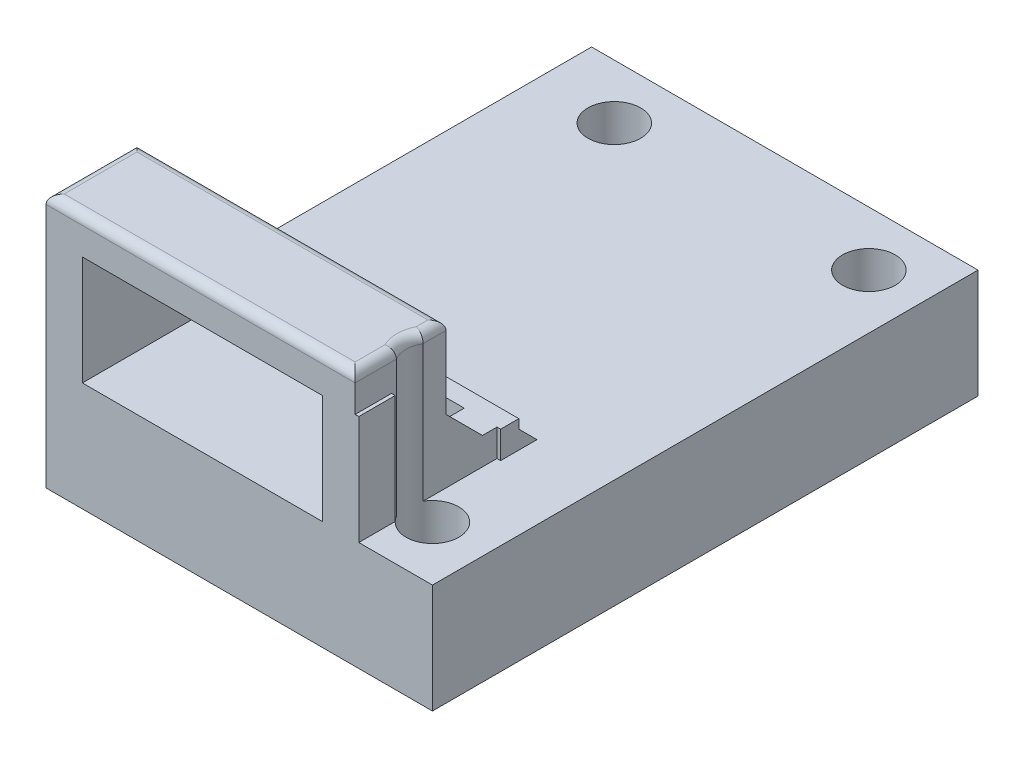
SolidWorks part; units mm, degrees
ref_plane "前视基准面" through (0, 0, 0) normal (0, 0, 1) x (1, 0, 0)
ref_plane "上视基准面" through (0, 0, 0) normal (0, 1, 0) x (1, 0, 0)
ref_plane "右视基准面" through (0, 0, 0) normal (1, 0, 0) x (0, 0, -1)
other "Configuration Table"
sketch "草图1" plane through (0, 0, 0) normal (0, 1, 0) x (1, 0, 0)
  line L0 (-21.25, 0) -> (-21.25, -5)
  line L2 (0, 0) -> (0, 10)
  line L3 (0, 10) -> (-21.25, 10)
  line L5 (-21.25, -5) -> (-6.25, -5)
  line L6 (-6.25, -5) -> (-6.25, 0)
  line L8 (-6.25, 0) -> (0, 0)
  line L10 (-21.25, 0) -> (-21.25, 10)
  dimension "D1" = 21.25
  dimension "D4" = 6.25
  dimension "D5" = 5
  dimension "D6" = 5
extrude "凸台-拉伸1" add sketch "草图1" along normal blind 4
sketch "草图7" plane through (0, 0, -10) normal (0, 0, -1) x (-1, 0, 0)
  line L1 (0, 4) -> (21.25, 4)
  line L2 (0, 4) -> (0, 0)
  line L3 (0, 0) -> (21.25, 0)
  line L4 (21.25, 4) -> (21.25, 0)
extrude "凸台-拉伸3" add sketch "草图7" along normal blind 15
sketch "草图8" plane through (0, 4, 0) normal (0, 1, 0) x (1, 0, 0)
  line L0 (0, 25) -> (-3, 25) construction
  line L1 (-21.25, 25) -> (0, 25) construction
  line L2 (-3, 25) -> (-17, 25) construction
  line L3 (-17, 25) -> (-17, 22) construction
  line L4 (-3, 25) -> (-3, 22) construction
  circle A2 centre (-17, 22) radius 1.45
  circle A3 centre (-3, 22) radius 1.45
  dimension "D3" = 3
  dimension "D5" = 2.9
  dimension "D6" = 2.9
  dimension "D1" = 3
  dimension "D2" = 14
  dimension "D4" = 3
extrude "切除-拉伸5" cut sketch "草图8" against normal blind 5
sketch "草图9" plane through (0, 0, 0) normal (0, 0, 1) x (1, 0, 0)
  line L1 (-6.25, 4) -> (0, 4)
  line L2 (-6.25, 4) -> (-6.25, 0)
  line L3 (-6.25, 0) -> (0, 0)
  line L4 (0, 4) -> (0, 0)
extrude "凸台-拉伸4" add sketch "草图9" along normal up to surface (5 mm away) up to face at (-13.75, 2, 5)
sketch "草图10" plane through (0, 4, 0) normal (0, 1, 0) x (1, 0, 0)
  line L0 (0, -5) -> (-3, -5) construction
  line L2 (-3, -5) -> (-3, -2) construction
  circle A0 centre (-3, -2) radius 1.45
  dimension "D3" = 2.9
  dimension "D1" = 3
  dimension "D2" = 3
extrude "切除-拉伸6" cut sketch "草图10" against normal blind 5
sketch "草图11" plane through (0, 4, 0) normal (0, 1, 0) x (1, 0, 0)
  line L0 (-21.25, -5) -> (0, -5) construction
  line L1 (-21.25, -5) -> (-19.25, -5)
  line L2 (-21.25, -5) -> (-21.25, -3)
  line L3 (-21.25, -3) -> (-19.25, -3)
  line L4 (-19.25, -5) -> (-19.25, -3)
  line L5 (-19.25, -3) -> (-6.05, -3) construction
  line L6 (-19.25, -3) -> (-19.25, 2.8) construction
  line L7 (-19.25, 2.8) -> (-6.05, 2.8) construction
  line L8 (-6.05, -3) -> (-6.05, 2.8) construction
  line L9 (-6.05, -3) -> (-4.05, -3)
  line L10 (-6.05, -3) -> (-6.05, -5)
  line L11 (-6.05, -5) -> (-4.05, -5)
  line L12 (-4.05, -3) -> (-4.05, -5)
  line L13 (-21.25, 25) -> (-21.25, -5) construction
  line L14 (-21.25, 3.8) -> (-18.75, 3.8)
  line L15 (-21.25, 3.8) -> (-21.25, 2.8)
  line L16 (-21.25, 2.8) -> (-18.75, 2.8)
  line L17 (-18.75, 3.8) -> (-18.75, 2.8)
  line L18 (-12.65, -3) -> (-12.65, 0.6579) construction
  line L19 (-4.05, 2.8) -> (-6.55, 2.8)
  line L20 (-6.55, 3.8) -> (-6.55, 2.8)
  line L21 (-4.05, 3.8) -> (-6.55, 3.8)
  line L22 (-4.05, 3.8) -> (-4.05, 2.8)
  dimension "D1" = 2
  dimension "D2" = 2
  dimension "D3" = 13.2
  dimension "D4" = 5.8
  dimension "D5" = 2
  dimension "D6" = 2.5
  dimension "D7" = 1
extrude "凸台-拉伸5" add sketch "草图11" along normal blind 6
sketch "草图12" plane through (0, 4, 0) normal (0, 1, 0) x (1, 0, 0)
  line L1 (-18.75, 3.8) -> (-6.55, 3.8)
  line L2 (-18.75, 3.8) -> (-18.75, 2.8)
  line L3 (-18.75, 2.8) -> (-6.55, 2.8)
  line L4 (-6.55, 3.8) -> (-6.55, 2.8)
  line L5 (-19.25, -3) -> (-21.25, -3)
  line L6 (-19.25, -3) -> (-19.25, 2.8)
  line L7 (-19.25, 2.8) -> (-21.25, 2.8)
  line L8 (-21.25, -3) -> (-21.25, 2.8)
  line L9 (-6.05, -3) -> (-4.25, -3)
  line L10 (-6.05, -3) -> (-6.05, 2.8)
  line L11 (-6.05, 2.8) -> (-4.25, 2.8)
  line L12 (-4.25, -3) -> (-4.25, 2.8)
extrude "凸台-拉伸6" add sketch "草图12" along normal blind 1.5
chamfer "倒角1" distance 1 angle 45 1 edges at (-12.65, 4, -3.8)
sketch "草图13" plane through (0, 5.5, 0) normal (0, 1, 0) x (1, 0, 0)
  circle A1 centre (-3, -2) radius 1.45 construction
  circle A2 centre (-3, -2) radius 1.45
extrude "切除-拉伸7" cut sketch "草图13" against normal blind 10
sketch "草图15" plane through (0, 10, 0) normal (0, 1, 0) x (1, 0, 0)
  line L1 (-4.25, -1.2652) -> (-4.25, 2.8) construction
  line L2 (-21.25, -5) -> (-4.25, -5)
  line L3 (-21.25, -5) -> (-21.25, 0)
  line L4 (-21.25, 0) -> (-4.25, 0)
  line L5 (-4.25, -5) -> (-4.25, 0)
extrude "凸台-拉伸7" add sketch "草图15" along normal blind 2
sketch "草图17" plane through (0, 5.5, 0) normal (0, 1, 0) x (1, 0, 0)
  line L0 (-19.25, -3) -> (-19.25, 2.8) construction
  line L2 (-21.25, 2.8) -> (-21.25, -3) construction
  line L3 (-21.25, -3) -> (-19.25, -3) construction
  line L4 (-4.25, -3) -> (-4.25, -2.7348) construction
  line L5 (-4.25, -1.2652) -> (-4.25, 2.8) construction
  line L7 (-6.05, 2.8) -> (-6.05, -3) construction
  line L8 (-6.05, -3) -> (-4.25, -3) construction
  line L9 (-19.25, -3) -> (-19.25, 0)
  line L11 (-21.25, 0) -> (-21.25, -3)
  line L12 (-21.25, -3) -> (-19.25, -3)
  line L13 (-4.25, -3) -> (-4.25, -2.7348)
  line L14 (-4.25, -1.2652) -> (-4.25, 0)
  line L16 (-6.05, 0) -> (-6.05, -3)
  line L17 (-6.05, -3) -> (-4.25, -3)
  line L18 (-4.25, 0) -> (-21.25, 0) construction
  line L19 (-4.25, 0) -> (-6.05, 0)
  line L20 (-19.25, 0) -> (-21.25, 0)
  arc A0 (-4.25, -1.2652) -> (-4.25, -2.7348) centre (-3, -2) ccw construction
  arc A1 (-4.25, -1.2652) -> (-4.25, -2.7348) centre (-3, -2) ccw
extrude "凸台-拉伸8" add sketch "草图17" along normal up to next
sketch "草图19" plane through (0, 12, 0) normal (0, 1, 0) x (1, 0, 0)
  line L1 (-4.25, -2.7348) -> (-4.25, -1.2652)
  line L4 (-4.25, -2.7348) -> (-4.25, -1.2652)
  arc A1 (-4.25, -1.2652) -> (-4.25, -2.7348) centre (-3, -2) ccw
  arc A4 (-4.25, -1.2652) -> (-4.25, -2.7348) centre (-3, -2) ccw
  dimension "D1" = 0
extrude "切除-拉伸9" cut sketch "草图19" against normal up to next
sketch "草图20" plane through (0, 10, 0) normal (0, 1, 0) x (1, 0, 0)
  line L0 (-4.05, 2.8) -> (-4.05, 3.8) construction
  line L1 (-4.05, 3.8) -> (-6.55, 3.8) construction
  line L2 (-6.55, 3.8) -> (-6.55, 2.8) construction
  line L3 (-6.55, 2.8) -> (-4.05, 2.8) construction
  line L4 (-21.25, 3.8) -> (-21.25, 2.8) construction
  line L5 (-21.25, 2.8) -> (-18.75, 2.8) construction
  line L6 (-18.75, 2.8) -> (-18.75, 3.8) construction
  line L7 (-18.75, 3.8) -> (-21.25, 3.8) construction
  line L8 (-4.05, 2.8) -> (-4.05, 3.8)
  line L9 (-4.05, 3.8) -> (-6.55, 3.8)
  line L10 (-6.55, 3.8) -> (-6.55, 2.8)
  line L11 (-6.55, 2.8) -> (-4.05, 2.8)
  line L12 (-21.25, 3.8) -> (-21.25, 2.8)
  line L13 (-21.25, 2.8) -> (-18.75, 2.8)
  line L14 (-18.75, 2.8) -> (-18.75, 3.8)
  line L15 (-18.75, 3.8) -> (-21.25, 3.8)
extrude "切除-拉伸10" cut sketch "草图20" against normal up to surface (4.5 mm away) up to face at (-20.25, 5.5, -1.4)
chamfer "倒角2" distance 2 angle 45 2 edges at (-20.25, 5.5, 0) (-5.15, 5.5, 0)
sketch "草图21" plane through (0, 0, 0) normal (0, -1, 0) x (1, 0, 0)
  line L4 (0, -25) -> (0, 5)
  line L5 (0, 5) -> (-21.25, 5)
  line L6 (-21.25, 5) -> (-21.25, -25)
  line L7 (-21.25, -25) -> (0, -25)
  line L8 (0, -25) -> (0, 5)
  line L9 (0, 5) -> (-21.25, 5)
  line L10 (-21.25, 5) -> (-21.25, -25)
  line L11 (-21.25, -25) -> (0, -25)
  circle A0 centre (-17, -22) radius 1.45 construction
  circle A1 centre (-3, -22) radius 1.45 construction
  circle A2 centre (-3, 2) radius 1.45 construction
  circle A3 centre (-17, -22) radius 1.45
  circle A4 centre (-3, -22) radius 1.45
  circle A5 centre (-3, 2) radius 1.45
  dimension "D1" = 0
extrude "凸台-拉伸10" add sketch "草图21" along normal blind 2
fillet "圆角2" radius 0.5 6 edges at (-12.75, 12, 5) (-21.25, 12, 2.5) (-12.75, 12, 0) (-4.25, 12, 0.6326) (-4.45, 12, 2) (-4.25, 12, 3.8674)
